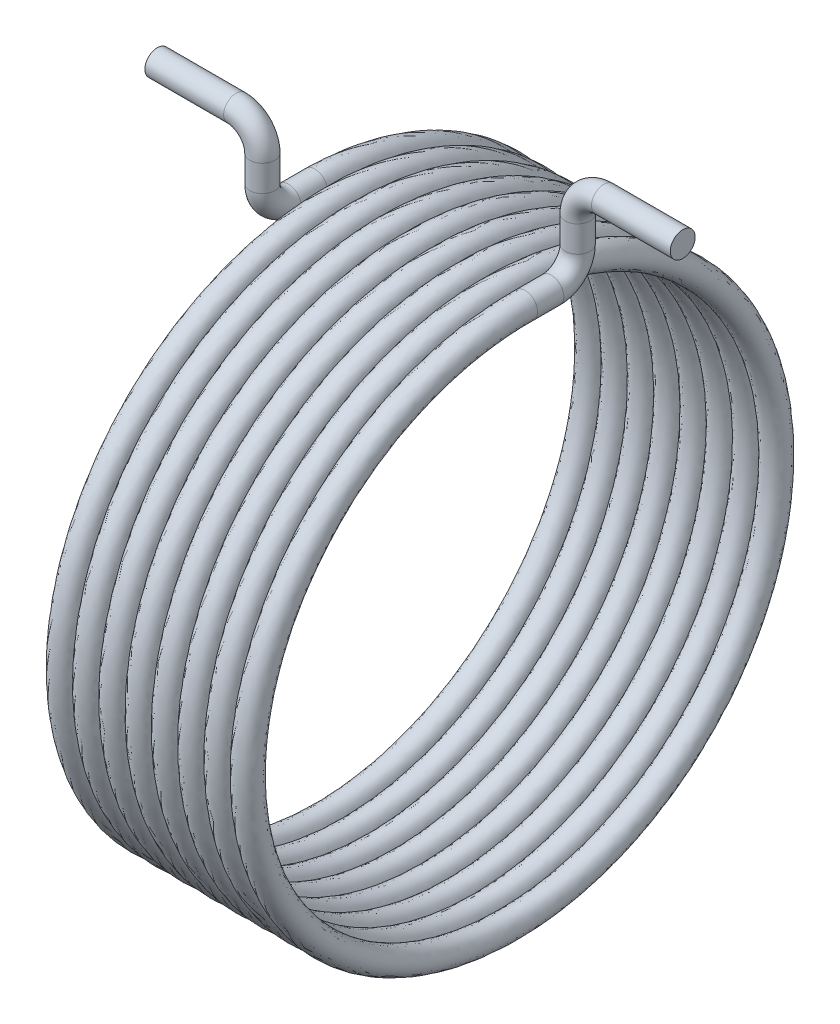
SolidWorks part; units mm, degrees
material "Plain Carbon Steel"
ref_plane "Front Plane" through (0, 0, 0) normal (0, 0, 1) x (1, 0, 0)
ref_plane "Top Plane" through (0, 0, 0) normal (0, 1, 0) x (1, 0, 0)
ref_plane "Right Plane" through (0, 0, 0) normal (1, 0, 0) x (0, 0, -1)
ref_plane "Plane2" through (-2.5, 0, 0) normal (1, 0, 0) x (0, 0, -1)
sketch "Sketch1" plane through (-2.5, 0, 0) normal (1, 0, 0) x (0, 0, -1)
  circle A0 centre (0, 0) radius 10 construction
  circle A1 centre (0.2479, 10.4971) radius 0.5 construction
  circle A2 centre (0, 0) radius 10.5
  dimension "D1" = 20
  dimension "D2" = 1
curve "Helix/Spiral1" pitch 1 height 8 radius 10.5 left hand yes centre (-2.5, 0, 0) axis (1, 0, 0) start towards (0, 1, 0)
sketch "Sketch2" plane through (0, 0, 0) normal (0, 0, 1) x (1, 0, 0)
  circle A0 centre (-2.4694, 10.3046) radius 0.475
  spline S0 degree 3 poles (-2.5, 10.5) (-2.4793, 10.5) (-2.4374, 9.9533) (-2.375, 7.6179) (-2.3125, 4.1228) (-2.25, 0) (-2.1875, -4.1228) (-2.125, -7.6179) (-2.0625, -9.9533) (-2, -10.7734) (-1.9375, -9.9533) (-1.875, -7.6179) (-1.8125, -4.1228) (-1.75, 0) (-1.6875, 4.1228) (-1.625, 7.6179) (-1.5625, 9.9533) (-1.5, 10.7734) (-1.4375, 9.9533) (-1.375, 7.6179) (-1.3125, 4.1228) (-1.25, 0) (-1.1875, -4.1228) (-1.125, -7.6179) (-1.0625, -9.9533) (-1, -10.7734) (-0.9375, -9.9533) (-0.875, -7.6179) (-0.8125, -4.1228) (-0.75, 0) (-0.6875, 4.1228) (-0.625, 7.6179) (-0.5625, 9.9533) (-0.5, 10.7734) (-0.4375, 9.9533) (-0.375, 7.6179) (-0.3125, 4.1228) (-0.25, 0) (-0.1875, -4.1228) (-0.125, -7.6179) (-0.0625, -9.9533) (0, -10.7734) (0.0625, -9.9533) (0.125, -7.6179) (0.1875, -4.1228) (0.25, 0) (0.3125, 4.1228) (0.375, 7.6179) (0.4375, 9.9533) (0.5, 10.7734) (0.5625, 9.9533) (0.625, 7.6179) (0.6875, 4.1228) (0.75, 0) (0.8125, -4.1228) (0.875, -7.6179) (0.9375, -9.9533) (1, -10.7734) (1.0625, -9.9533) (1.125, -7.6179) (1.1875, -4.1228) (1.25, 0) (1.3125, 4.1228) (1.375, 7.6179) (1.4375, 9.9533) (1.5, 10.7734) (1.5625, 9.9533) (1.625, 7.6179) (1.6875, 4.1228) (1.75, 0) (1.8125, -4.1228) (1.875, -7.6179) (1.9375, -9.9533) (2, -10.7734) (2.0625, -9.9533) (2.125, -7.6179) (2.1875, -4.1228) (2.25, 0) (2.3125, 4.1228) (2.375, 7.6179) (2.4375, 9.9533) (2.5, 10.7734) (2.5625, 9.9533) (2.625, 7.6179) (2.6875, 4.1228) (2.75, 0) (2.8125, -4.1228) (2.875, -7.6179) (2.9375, -9.9533) (3, -10.7734) (3.0625, -9.9533) (3.125, -7.6179) (3.1875, -4.1228) (3.25, 0) (3.3125, 4.1228) (3.375, 7.6179) (3.4375, 9.9533) (3.5, 10.7734) (3.5625, 9.9533) (3.625, 7.6179) (3.6875, 4.1228) (3.75, 0) (3.8125, -4.1228) (3.875, -7.6179) (3.9375, -9.9533) (4, -10.7734) (4.0625, -9.9533) (4.125, -7.6179) (4.1875, -4.1228) (4.25, 0) (4.3125, 4.1228) (4.375, 7.6179) (4.4375, 9.9533) (4.5, 10.7734) (4.5625, 9.9533) (4.625, 7.6179) (4.6875, 4.1228) (4.75, 0) (4.8125, -4.1228) (4.875, -7.6179) (4.9375, -9.9533) (5, -10.7734) (5.0625, -9.9533) (5.125, -7.6179) (5.1875, -4.1228) (5.25, 0) (5.3125, 4.1228) (5.375, 7.6179) (5.4374, 9.9533) (5.4793, 10.5) (5.5, 10.5) knots 0 0 0 0 0.007813 0.015625 0.023438 0.03125 0.039063 0.046875 0.054688 0.0625 0.070313 0.078125 0.085938 0.09375 0.101563 0.109375 0.117188 0.125 0.132813 0.140625 0.148438 0.15625 0.164063 0.171875 0.179688 0.1875 0.195313 0.203125 0.210938 0.21875 0.226563 0.234375 0.242188 0.25 0.257813 0.265625 0.273438 0.28125 0.289063 0.296875 0.304688 0.3125 0.320313 0.328125 0.335938 0.34375 0.351563 0.359375 0.367188 0.375 0.382813 0.390625 0.398438 0.40625 0.414063 0.421875 0.429688 0.4375 0.445313 0.453125 0.460938 0.46875 0.476563 0.484375 0.492188 0.5 0.507813 0.515625 0.523438 0.53125 0.539063 0.546875 0.554688 0.5625 0.570313 0.578125 0.585938 0.59375 0.601563 0.609375 0.617188 0.625 0.632813 0.640625 0.648438 0.65625 0.664063 0.671875 0.679688 0.6875 0.695313 0.703125 0.710938 0.71875 0.726563 0.734375 0.742188 0.75 0.757813 0.765625 0.773438 0.78125 0.789063 0.796875 0.804688 0.8125 0.820313 0.828125 0.835938 0.84375 0.851563 0.859375 0.867188 0.875 0.882813 0.890625 0.898438 0.90625 0.914063 0.921875 0.929688 0.9375 0.945313 0.953125 0.960938 0.96875 0.976563 0.984375 0.992188 1 1 1 1 construction
  dimension "D1" = 0.95
sweep "Sweep1" add profiles "Sketch2" path "Helix/Spiral1"
ref_axis "Axis1" through (-0.7725, 0, 0) along (1, 0, 0)
sketch "Sketch3" plane through (0, 0, 0) normal (0, 0, 1) x (1, 0, 0)
  circle A0 centre (-2.4694, 10.3046) radius 0.475 construction
  circle A2 centre (-2.4694, 10.3046) radius 0.475
ref_plane "Plane1" through (-2.4694, 0, 0) normal (1, 0, 0) x (0, 0, -1)
sketch "Sketch5" plane through (0, 0, 0) normal (0, 0, -1) x (-1, 0, 0)
  circle A0 centre (-5.5306, 10.3046) radius 0.475 construction
  circle A1 centre (-5.5306, 10.3046) radius 0.475
sketch3d "3DSketch1"
  line L0 (-2.4694, 10.3046, 0) -> (-2.4694, 10.3046, 1)
  line L1 (-2.4694, 11.3046, 2) -> (-2.4694, 12.3046, 2)
  line L2 (-3.4694, 13.3046, 2) -> (-6.4694, 13.3046, 2)
  arc A0 (-2.4694, 10.3046, 1) -> (-2.4694, 11.3046, 2) centre (-2.4694, 11.3046, 1) ccw
  arc A1 (-2.4694, 12.3046, 2) -> (-3.4694, 13.3046, 2) centre (-3.4694, 12.3046, 2) ccw
  circle A2 centre (-2.4694, 10.3046, 0) radius 0.475 construction
  circle A3 centre (-2.4694, 10.3046, 0) radius 0.475 construction
  point P4 (-3.4694, 11.3046, 1)
  point P8 (-3.4694, 12.3046, 3)
  point P13 (-2.4694, 10.3046, 0.475)
  point P14 (-2.4694, 10.3046, 0.475)
  dimension "D2" = 1
  dimension "D1" = 1
  dimension "D3" = 3
sweep "Sweep4" add profiles "Sketch3" path "3DSketch1"
ref_axis "Axis2" through (-3.4694, 13.3046, 2) along (-1, 0, 0)
sketch3d "3DSketch2"
  line L0 (5.5306, 10.3046, 0) -> (5.5306, 10.3046, -1)
  line L1 (5.5306, 11.3046, -2) -> (5.5306, 12.3046, -2)
  line L2 (6.5306, 13.3046, -2) -> (9.5306, 13.3046, -2)
  arc A0 (5.5306, 10.3046, -1) -> (5.5306, 11.3046, -2) centre (5.5306, 11.3046, -1) ccw
  arc A1 (5.5306, 12.3046, -2) -> (6.5306, 13.3046, -2) centre (6.5306, 12.3046, -2) ccw
  circle A2 centre (5.5306, 10.3046, 0) radius 0.475 construction
  circle A3 centre (5.5306, 10.3046, 0) radius 0.475 construction
  point P3 (6.5306, 11.3046, -1)
  point P7 (6.5306, 12.3046, -3)
  point P12 (5.5306, 10.3046, -0.475)
  point P14 (5.5306, 10.3046, -0.475)
  dimension "D2" = 1
  dimension "D1" = 1
  dimension "D3" = 3
sweep "Sweep5" add profiles "Sketch5" path "3DSketch2"
ref_axis "Axis3" through (2.3138, 13.3046, -2) along (1, 0, 0)
